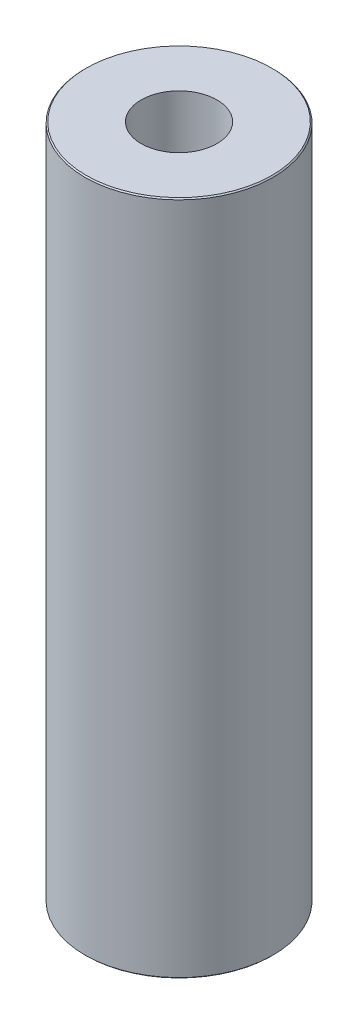
SolidWorks part; units mm, degrees
ref_plane "Front Plane" through (0, 0, 0) normal (0, 0, 1) x (1, 0, 0)
ref_plane "Top Plane" through (0, 0, 0) normal (0, 1, 0) x (1, 0, 0)
ref_plane "Right Plane" through (0, 0, 0) normal (1, 0, 0) x (0, 0, -1)
sketch "Sketch1" plane through (0, 0, 0) normal (0, 1, 0) x (1, 0, 0)
  circle A0 centre (0, 0) radius 27.5
  dimension "SHAFT_OD" = 55
extrude "Boss-Extrude1" add sketch "Sketch1" along normal blind 197.6172
sketch "Sketch2" plane through (0, 0, 0) normal (0, 1, 0) x (1, 0, 0)
  circle A0 centre (0, 0) radius 11.087
  dimension "BORE_D" = 22.174
extrude "Cut-Extrude1" cut sketch "Sketch2" along normal through all
chamfer "Chamfer1" distance 0.3417 angle 45 2 edges at (0, 197.6172, 27.5) (0, 0, 27.5)
